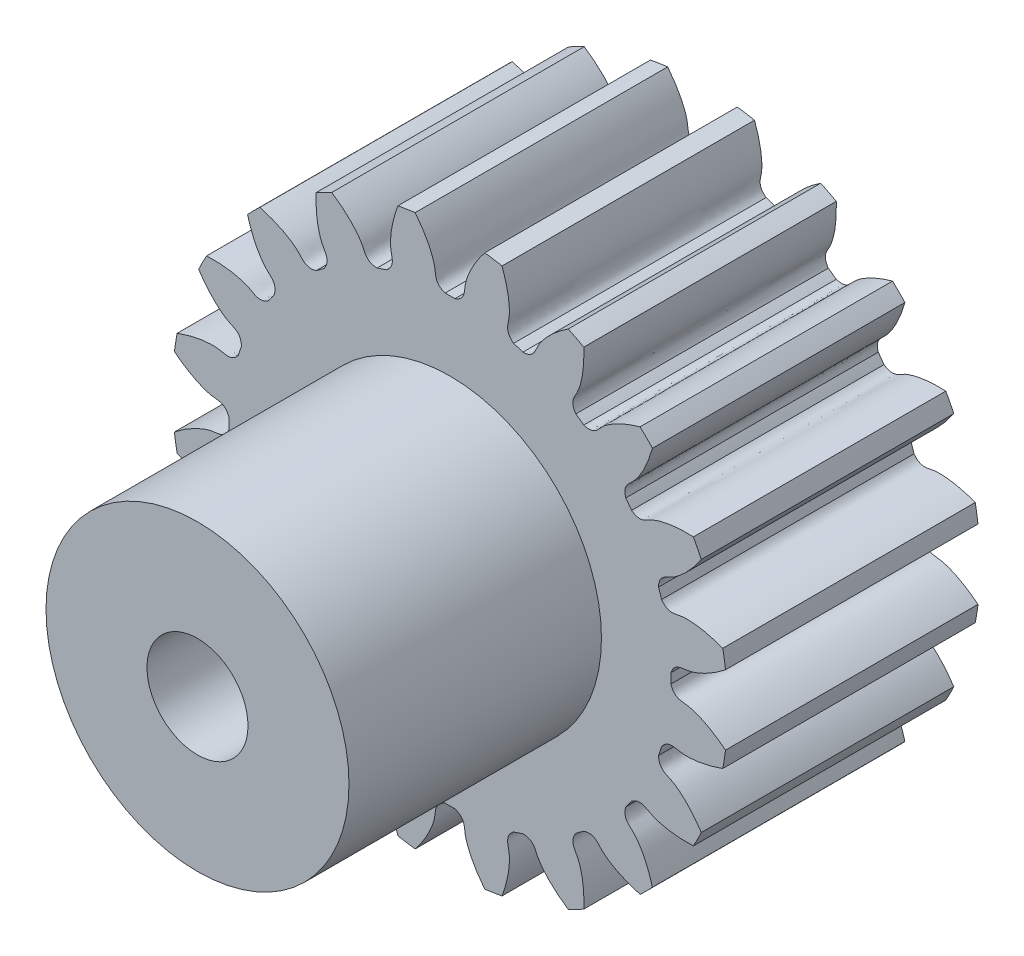
SolidWorks part; units mm, degrees
ref_plane "前视基准面" through (0, 0, 0) normal (0, 0, 1) x (1, 0, 0)
ref_plane "上视基准面" through (0, 0, 0) normal (0, 1, 0) x (1, 0, 0)
ref_plane "右视基准面" through (0, 0, 0) normal (1, 0, 0) x (0, 0, -1)
sketch "草图1" plane through (0, 0, 0) normal (0, 0, 1) x (1, 0, 0)
  circle A0 centre (0, 0) radius 5.5
extrude "凸台-拉伸1" add sketch "草图1" along normal blind 5
ref_axis "基准轴1" through (0, 0, 5) along (0, 0, -1)
sketch "草图2" plane through (0, 0, 0) normal (0, 0, 1) x (1, 0, 0)
  line L0 (0, 0) -> (0, 5.5) construction
  circle A0 centre (0, 0) radius 5.5 construction
  arc A1 (0.0967, 4.3739) -> (-0.0967, 4.3739) centre (0, 0) ccw
  arc A2 (1.5906, 6.2491) -> (-1.5906, 6.2491) centre (0, 0) ccw
  spline S0 degree 3 poles (0.0967, 4.3739) (0.3056, 4.4467) (0.2785, 4.5936) (0.3064, 4.735) (0.3094, 4.7488) (0.3132, 4.7643) (0.3176, 4.7816) (0.323, 4.8006) (0.3293, 4.8213) (0.3365, 4.8436) (0.3448, 4.8676) (0.3543, 4.8932) (0.3649, 4.9203) (0.3768, 4.9489) (0.3901, 4.979) (0.4047, 5.0106) (0.4208, 5.0435) (0.4383, 5.0778) (0.4575, 5.1134) (0.4783, 5.1502) (0.5008, 5.1882) (0.525, 5.2274) (0.551, 5.2676) (0.5789, 5.3089) (0.6087, 5.3511) (0.6404, 5.3943) (0.6741, 5.4383) (0.7099, 5.4831) (0.7477, 5.5286) (0.7877, 5.5748) (0.8299, 5.6215) (0.8743, 5.6688) (0.9209, 5.7165) (0.9698, 5.7646) (1.0211, 5.813) (1.0747, 5.8617) (1.1306, 5.9104) (1.189, 5.9593) (1.2498, 6.0082) (1.313, 6.057) (1.3788, 6.1056) (1.4707, 6.1708) (1.542, 6.2182) (1.5906, 6.2491) knots 0 0 0 0 0.165916 0.170906 0.176664 0.183189 0.190482 0.198542 0.207371 0.216967 0.22733 0.238462 0.250361 0.263027 0.276462 0.290664 0.305634 0.321371 0.337876 0.355149 0.37319 0.391998 0.411574 0.431917 0.453028 0.474907 0.497554 0.520968 0.54515 0.570099 0.595817 0.622302 0.649554 0.677575 0.706363 0.735918 0.766242 0.797333 0.829191 0.861818 0.895212 0.929373 1 1 1 1
  spline S1 degree 3 poles (-0.0967, 4.3739) (-0.3056, 4.4467) (-0.2785, 4.5936) (-0.3064, 4.735) (-0.3094, 4.7488) (-0.3132, 4.7643) (-0.3176, 4.7816) (-0.323, 4.8006) (-0.3293, 4.8213) (-0.3365, 4.8436) (-0.3448, 4.8676) (-0.3543, 4.8932) (-0.3649, 4.9203) (-0.3768, 4.9489) (-0.3901, 4.979) (-0.4047, 5.0106) (-0.4208, 5.0435) (-0.4383, 5.0778) (-0.4575, 5.1134) (-0.4783, 5.1502) (-0.5008, 5.1882) (-0.525, 5.2274) (-0.551, 5.2676) (-0.5789, 5.3089) (-0.6087, 5.3511) (-0.6404, 5.3943) (-0.6741, 5.4383) (-0.7099, 5.4831) (-0.7477, 5.5286) (-0.7877, 5.5748) (-0.8299, 5.6215) (-0.8743, 5.6688) (-0.9209, 5.7165) (-0.9698, 5.7646) (-1.0211, 5.813) (-1.0747, 5.8617) (-1.1306, 5.9104) (-1.189, 5.9593) (-1.2498, 6.0082) (-1.313, 6.057) (-1.3788, 6.1056) (-1.4707, 6.1708) (-1.542, 6.2182) (-1.5906, 6.2491) knots 0 0 0 0 0.165916 0.170906 0.176664 0.183189 0.190482 0.198542 0.207371 0.216967 0.22733 0.238462 0.250361 0.263027 0.276462 0.290664 0.305634 0.321371 0.337876 0.355149 0.37319 0.391998 0.411574 0.431917 0.453028 0.474907 0.497554 0.520968 0.54515 0.570099 0.595817 0.622302 0.649554 0.677575 0.706363 0.735918 0.766242 0.797333 0.829191 0.861818 0.895212 0.929373 1 1 1 1
extrude "切除-拉伸1" cut sketch "草图2" along normal through all
pattern_circular "阵列(圆周)1" count 20 every 18 about axis through (0, 0, 5) along (0, 0, -1) of "切除-拉伸1"
sketch "草图3" plane through (0, 0, 0) normal (0, 0, 1) x (1, 0, 0)
  circle A0 centre (0, 0) radius 5 construction
  dimension "Dn" = 10
sketch "草图5" plane through (0, 0, 5) normal (0, 0, 1) x (1, 0, 0)
  circle A0 centre (0, 0) radius 1
  circle A1 centre (0, 0) radius 3
  dimension "D1" = 2
  dimension "D2" = 6
extrude "凸台-拉伸2" add sketch "草图5" along normal blind 5
